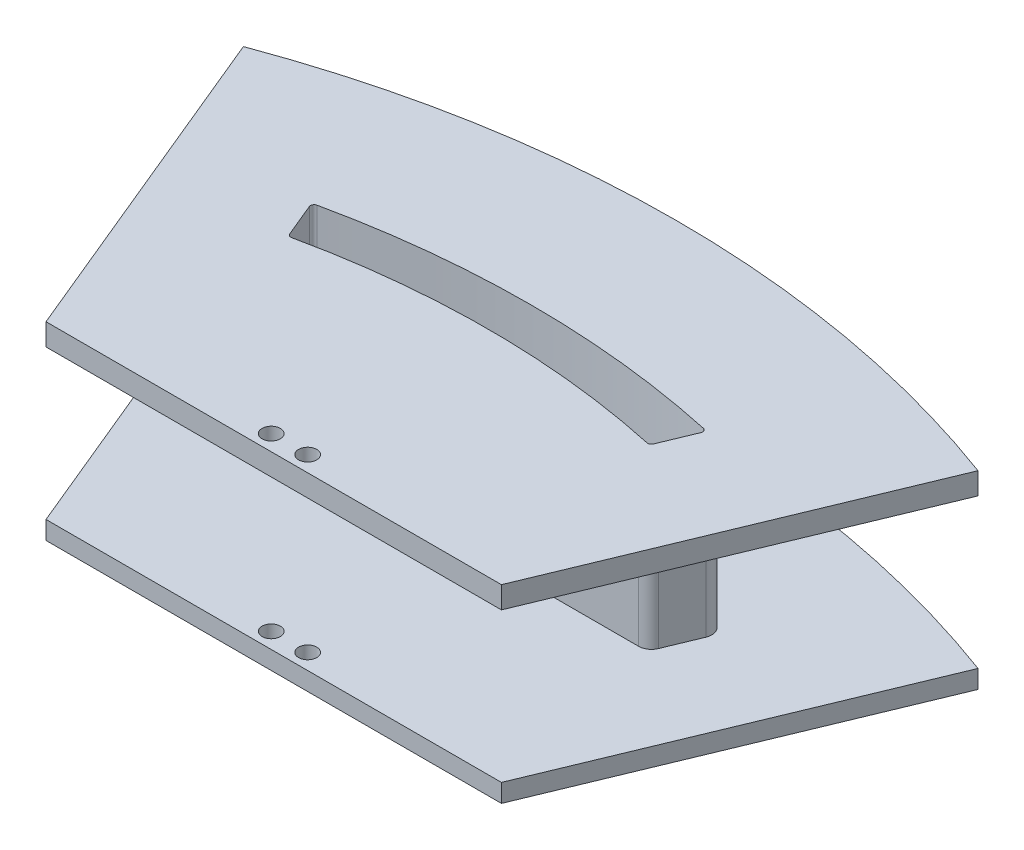
SolidWorks part; units mm, degrees
ref_plane "Front Plane" through (0, 0, 0) normal (0, 0, 1) x (1, 0, 0)
ref_plane "Top Plane" through (0, 0, 0) normal (0, 1, 0) x (1, 0, 0)
ref_plane "Right Plane" through (0, 0, 0) normal (1, 0, 0) x (0, 0, -1)
sketch "Sketch1" plane through (0, 0, 0) normal (0, 1, 0) x (1, 0, 0)
  line L0 (-50.4049, 135.9571) -> (-31.25, 89.7131)
  line L1 (0, 0) -> (0, 192.2134) construction
  line L2 (50.4049, 135.9571) -> (31.25, 89.7131)
  line L3 (-28.7185, 120.7102) -> (-26.8051, 116.0908) construction
  line L4 (28.7185, 120.7102) -> (26.8051, 116.0908) construction
  line L5 (-28.0256, 120.9972) -> (-26.1122, 116.3778)
  line L6 (-24.4954, 115.2975) -> (24.4954, 115.2975)
  line L7 (-26.8707, 121.4755) -> (-24.9573, 116.8561)
  line L8 (26.8707, 121.4755) -> (24.9573, 116.8561)
  line L12 (-31.25, 89.7131) -> (31.25, 89.7131)
  line L13 (-24.4954, 114.5475) -> (24.4954, 114.5475) construction
  line L14 (0, 127) -> (-30.0054, 127) construction
  line L15 (0, 145) -> (-27.091, 145) construction
  line L16 (28.0256, 120.9972) -> (26.1122, 116.3778)
  circle A0 centre (0, 0) radius 145 construction
  arc A1 (-31.25, 89.7131) -> (31.25, 89.7131) centre (0, 0) ccw construction
  arc A2 (-50.4049, 135.9571) -> (50.4049, 135.9571) centre (0, 0) cw
  arc A3 (31.25, 89.7131) -> (5, 94.8683) centre (0, 0) ccw construction
  arc A4 (0, 117.1749) -> (-23.9652, 114.6043) centre (0, 4.1749) ccw construction
  arc A5 (-26.9391, 124.11) -> (26.9391, 124.11) centre (0, 0) cw construction
  arc A6 (-26.1122, 116.3778) -> (-24.4954, 115.2975) centre (-24.4954, 117.0475) ccw
  arc A7 (26.9391, 124.11) -> (28.7185, 120.7102) centre (26.4088, 121.6669) cw construction
  arc A8 (26.1122, 116.3778) -> (24.4954, 115.2975) centre (24.4954, 117.0475) cw
  arc A9 (26.8051, 116.0908) -> (24.4954, 114.5475) centre (24.4954, 117.0475) cw construction
  arc A10 (-26.8051, 116.0908) -> (-24.4954, 114.5475) centre (-24.4954, 117.0475) ccw construction
  arc A11 (-28.7185, 120.7102) -> (-26.9391, 124.11) centre (-26.4088, 121.6669) cw construction
  arc A12 (24.3893, 116.5588) -> (-24.3893, 116.5588) centre (0, 4.1749) ccw
  arc A13 (-24.9573, 116.8561) -> (-24.3893, 116.5588) centre (-24.4954, 117.0475) ccw
  arc A14 (-26.8707, 121.4755) -> (-26.5149, 122.1555) centre (-26.4088, 121.6669) cw
  arc A15 (-26.5149, 122.1555) -> (26.5149, 122.1555) centre (0, 0) cw
  arc A16 (26.5149, 122.1555) -> (26.8707, 121.4755) centre (26.4088, 121.6669) cw
  arc A17 (24.9573, 116.8561) -> (24.3893, 116.5588) centre (24.4954, 117.0475) cw
  arc A18 (0, 95) -> (-5, 94.8683) centre (0, 0) ccw construction
  arc A19 (-5, 94.8683) -> (-31.25, 89.7131) centre (0, 0) ccw construction
  arc A20 (26.78, 123.377) -> (28.0256, 120.9972) centre (26.4088, 121.6669) cw
  arc A21 (0, 95) -> (-5, 94.8683) centre (0, 0) ccw construction
  arc A22 (5, 94.8683) -> (0, 95) centre (0, 0) ccw construction
  arc A23 (5, 94.8683) -> (0, 95) centre (0, 0) ccw construction
  circle A24 centre (-2.5, 91.8683) radius 1.25
  circle A25 centre (2.5, 91.8683) radius 1.25
  arc A26 (-5, 94.8683) -> (-31.25, 89.7131) centre (0, 0) ccw construction
  arc A27 (31.25, 89.7131) -> (5, 94.8683) centre (0, 0) ccw construction
  arc A28 (24.4954, 114.5475) -> (23.9652, 114.6043) centre (24.4954, 117.0475) cw construction
  arc A29 (26.8051, 116.0908) -> (23.9652, 114.6043) centre (24.4954, 117.0475) cw construction
  arc A30 (23.9652, 114.6043) -> (0, 117.1749) centre (0, 4.1749) ccw construction
  arc A31 (23.9652, 114.6043) -> (-23.9652, 114.6043) centre (0, 4.1749) ccw construction
  arc A32 (-24.4954, 114.5475) -> (-23.9652, 114.6043) centre (-24.4954, 117.0475) ccw construction
  arc A33 (-26.8051, 116.0908) -> (-23.9652, 114.6043) centre (-24.4954, 117.0475) ccw construction
  arc A34 (-26.78, 123.377) -> (26.78, 123.377) centre (0, 0) cw
  arc A35 (-28.0256, 120.9972) -> (-26.78, 123.377) centre (-26.4088, 121.6669) cw
  dimension "D1" = 290
  dimension "D2" = 190
  dimension "D4" = 5
  dimension "D5" = 2.5
  dimension "D10" = 2.5
  dimension "D8" = 115
  dimension "D9" = 125
  dimension "D3" = 22.5
  dimension "D7" = 62.5
  dimension "D11" = 45
  dimension "D12" = 0.75
  dimension "D6" = 4.1749
extrude "Boss-Extrude1" add sketch "Sketch1" against normal blind 2.5 contours A25 | L0 L12 L2 A2 | A12 A13 L7 A14 A15 A16 L8 A17 | A24 region at (2.5, 0, -91.8683)
extrude "Boss-Extrude2" add sketch "Sketch1<3>" along normal blind 26 from surface contours A35 L5 A6 L6 A8 L16 A20 A34 L8 A17 A12 A13 L7 A14 A15 A16 region at (-27.451, 0, -122.2123) starting at face at (-2.5, -2.5, -90.6183)
sketch "Sketch1<3>" plane through (0, 0, 0) normal (0, 1, 0) x (1, 0, 0) same geometry as "Sketch1"
extrude "Boss-Extrude3" add sketch "Sketch1<4>" against normal blind 3 from surface contours A35 L5 A6 L6 A8 L16 A20 A34 L8 A17 A12 A13 L7 A14 A15 A16 | A2 L0 L12 L2 A25 A24 L5 A35 A34 A20 L16 A8 L6 A6 region at (0, 0, -143.8502) region at (-27.451, 0, -122.2123) starting at face at (0, 23.5, -119.383)
sketch "Sketch1<4>" plane through (0, 0, 0) normal (0, 1, 0) x (1, 0, 0) same geometry as "Sketch1"
sketch "Sketch2" plane through (0, 23.5, 0) normal (0, 1, 0) x (1, 0, 0)
  line L0 (24.9573, 116.8561) -> (26.8707, 121.4755) construction
  line L1 (-24.9573, 116.8561) -> (-26.8707, 121.4755) construction
  line L2 (24.9573, 116.8561) -> (26.8707, 121.4755)
  line L3 (-24.9573, 116.8561) -> (-26.8707, 121.4755)
  arc A0 (24.3893, 116.5588) -> (24.9573, 116.8561) centre (24.4954, 117.0475) ccw construction
  arc A1 (26.8707, 121.4755) -> (26.5149, 122.1555) centre (26.4088, 121.6669) ccw construction
  arc A2 (26.5149, 122.1555) -> (-26.5149, 122.1555) centre (0, 0) ccw construction
  arc A3 (-26.5149, 122.1555) -> (-26.8707, 121.4755) centre (-26.4088, 121.6669) ccw construction
  arc A4 (-24.9573, 116.8561) -> (-24.3893, 116.5588) centre (-24.4954, 117.0475) ccw construction
  arc A5 (24.3893, 116.5588) -> (-24.3893, 116.5588) centre (0, 4.1749) ccw construction
  arc A6 (24.3893, 116.5588) -> (24.9573, 116.8561) centre (24.4954, 117.0475) ccw
  arc A7 (26.8707, 121.4755) -> (26.5149, 122.1555) centre (26.4088, 121.6669) ccw
  arc A8 (26.5149, 122.1555) -> (-26.5149, 122.1555) centre (0, 0) ccw
  arc A9 (-26.5149, 122.1555) -> (-26.8707, 121.4755) centre (-26.4088, 121.6669) ccw
  arc A10 (-24.9573, 116.8561) -> (-24.3893, 116.5588) centre (-24.4954, 117.0475) ccw
  arc A11 (24.3893, 116.5588) -> (-24.3893, 116.5588) centre (0, 4.1749) ccw
